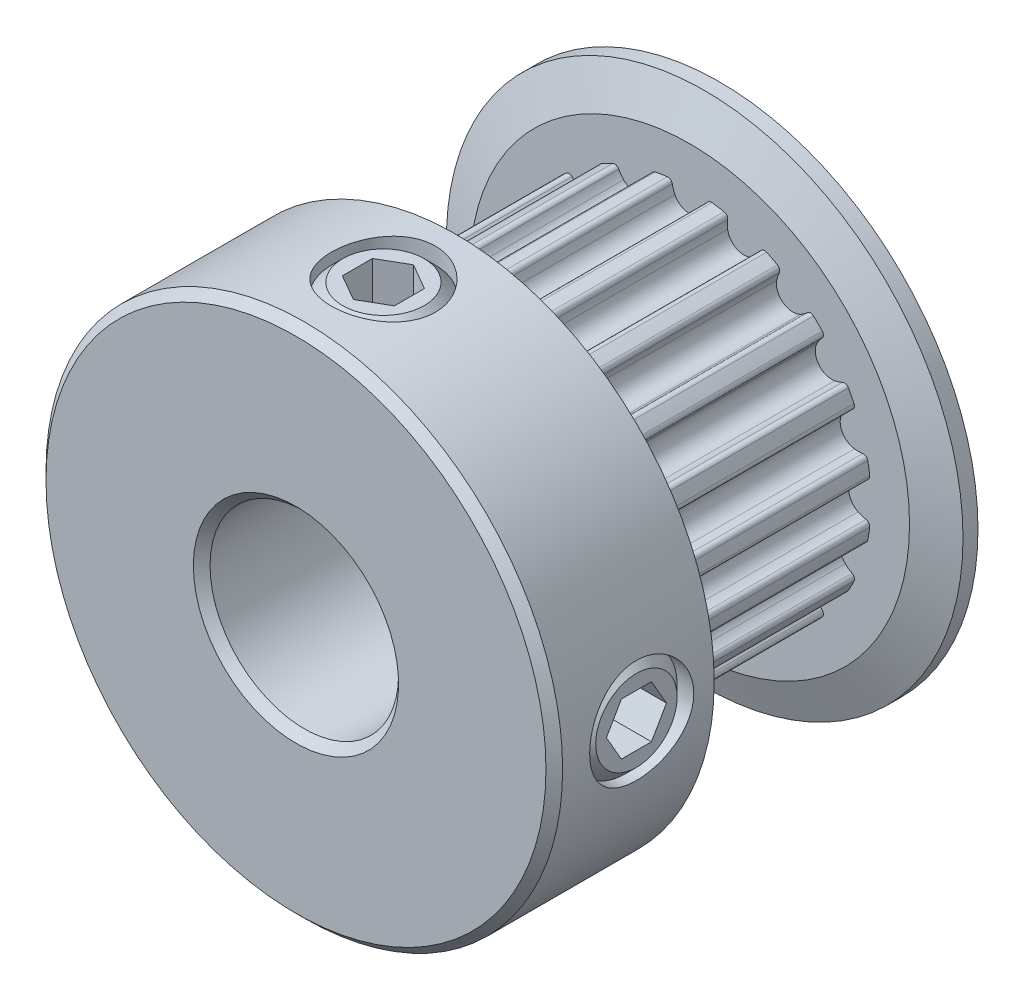
SolidWorks part; units mm, degrees
ref_plane "Front Plane" through (0, 0, 0) normal (0, 0, 1) x (1, 0, 0)
ref_plane "Top Plane" through (0, 0, 0) normal (0, 1, 0) x (1, 0, 0)
ref_plane "Right Plane" through (0, 0, 0) normal (1, 0, 0) x (0, 0, -1)
sketch "Sketch1" plane through (0, 0, 0) normal (0, 0, 1) x (1, 0, 0)
  line L1 (-1.7499, 5.3585) -> (1.7499, 5.3585) construction
  line L4 (0, 0) -> (0, 5.3585) construction
  line L5 (0, 5.3585) -> (0, 11.2113) construction
  line L6 (0, 6.3625) -> (1.9751, 6.0482) construction
  line L7 (1.9751, 6.0482) -> (2.6648, 5.8229) construction
  line L8 (1.9751, 6.0482) -> (1.7499, 5.3585) construction
  line L9 (-1.9751, 6.0482) -> (-1.7499, 5.3585) construction
  line L10 (-1.8963, 5.8067) -> (-2.841, 8.6995)
  line L11 (-2.841, 8.6995) -> (2.841, 8.6995)
  line L12 (2.841, 8.6995) -> (1.8963, 5.8067)
  circle A0 centre (0, 0) radius 6.3625 construction
  circle A1 centre (0, 0) radius 8.6995 construction
  circle A2 centre (0, 0) radius 6.1085 construction
  arc A3 (-0.4989, 5.6703) -> (0.4989, 5.6703) centre (0, 5.9135) ccw
  arc A4 (-0.4989, 5.6703) -> (-0.5855, 5.9387) centre (0.4, 6.1085) cw
  arc A5 (-1.8963, 5.8067) -> (-0.7518, 6.0621) centre (0, 0) cw
  arc A6 (-0.5855, 5.9387) -> (-0.7518, 6.0621) centre (-0.7333, 5.9132) ccw
  arc A7 (1.8963, 5.8067) -> (0.7518, 6.0621) centre (0, 0) ccw
  arc A8 (0.5855, 5.9387) -> (0.7518, 6.0621) centre (0.7333, 5.9132) cw
  arc A9 (0.4989, 5.6703) -> (0.5855, 5.9387) centre (-0.4, 6.1085) ccw
  point P6 (0, 20.9083)
  point P11 (0, 6.3625)
  point P13 (0, 8.6995)
  point P14 (0, 6.1085)
  dimension "D1" = 9.697
  dimension "D2" = 4.8488
sketch "Sketch2" plane through (0, 0, 0) normal (1, 0, 0) x (0, 0, -1)
  line L0 (-7.135, 3.175) -> (7.135, 3.175)
  line L1 (-7.135, 3.175) -> (-7.135, 8.6995)
  line L2 (-1.75, 8.6995) -> (-7.135, 8.6995)
  line L3 (-2.255, 3.175) -> (-2.255, 8.6995) construction
  line L4 (-2.255, 8.6995) -> (-1.245, 8.6995) construction
  line L5 (-1.245, 8.6995) -> (-1.245, 6.1085) construction
  line L6 (-1.245, 6.1085) -> (6.125, 6.1085)
  line L7 (6.125, 6.1085) -> (6.125, 8.6995) construction
  line L8 (6.125, 8.6995) -> (7.135, 8.6995) construction
  line L9 (7.135, 8.6995) -> (7.135, 3.175)
  line L10 (-7.135, 0) -> (7.135, 0) construction
  line L11 (6.63, 8.6995) -> (6.125, 7.404)
  line L12 (-1.245, 7.404) -> (-1.75, 8.6995)
  line L14 (-1.245, 7.404) -> (-1.245, 6.1085)
  line L15 (6.125, 6.1085) -> (6.125, 7.404)
  line L16 (6.63, 8.6995) -> (7.135, 8.6995)
  arc A0 (-1.245, 7.404) -> (-1.75, 8.6995) centre (-3.1592, 7.404) ccw construction
  arc A1 (6.125, 7.404) -> (6.63, 8.6995) centre (8.0392, 7.404) cw construction
  point P12 (-1.245, 7.404)
  point P14 (-1.75, 8.6995)
  point P20 (6.125, 7.404)
  point P21 (6.63, 8.6995)
  point P25 (6.125, 0)
  point P26 (-1.245, 0)
  dimension "OA" = 14.27
  dimension "Bore" = 6.35
  dimension "Outside Width" = 8.38
  dimension "Inside Width" = 7.37
revolve "Revolve1" add sketch "Sketch2" angle 360 mid plane about L10
sketch "Sketch3" plane through (0, 0, 0) normal (0, 0, 1) x (1, 0, 0)
  line L6 (2.841, 8.6995) -> (-2.841, 8.6995)
  line L7 (1.8963, 5.8067) -> (2.841, 8.6995)
  line L8 (-2.841, 8.6995) -> (-1.8963, 5.8067)
  line L9 (2.841, 8.6995) -> (-2.841, 8.6995)
  line L10 (1.8963, 5.8067) -> (2.841, 8.6995)
  line L11 (-2.841, 8.6995) -> (-1.8963, 5.8067)
  arc A8 (1.8963, 5.8067) -> (0.7518, 6.0621) centre (0, 0) ccw
  arc A9 (0.7518, 6.0621) -> (0.5855, 5.9387) centre (0.7333, 5.9132) ccw
  arc A10 (0.4989, 5.6703) -> (0.5855, 5.9387) centre (-0.4, 6.1085) ccw
  arc A11 (-0.4989, 5.6703) -> (0.4989, 5.6703) centre (0, 5.9135) ccw
  arc A12 (-0.5855, 5.9387) -> (-0.4989, 5.6703) centre (0.4, 6.1085) ccw
  arc A13 (-0.5855, 5.9387) -> (-0.7518, 6.0621) centre (-0.7333, 5.9132) ccw
  arc A14 (-0.7518, 6.0621) -> (-1.8963, 5.8067) centre (0, 0) ccw
  arc A15 (1.8963, 5.8067) -> (0.7518, 6.0621) centre (0, 0) ccw
  arc A16 (0.7518, 6.0621) -> (0.5855, 5.9387) centre (0.7333, 5.9132) ccw
  arc A17 (0.4989, 5.6703) -> (0.5855, 5.9387) centre (-0.4, 6.1085) ccw
  arc A18 (-0.4989, 5.6703) -> (0.4989, 5.6703) centre (0, 5.9135) ccw
  arc A19 (-0.5855, 5.9387) -> (-0.4989, 5.6703) centre (0.4, 6.1085) ccw
  arc A20 (-0.5855, 5.9387) -> (-0.7518, 6.0621) centre (-0.7333, 5.9132) ccw
  arc A21 (-0.7518, 6.0621) -> (-1.8963, 5.8067) centre (0, 0) ccw
  dimension "D1" = 0
extrude "Cut-Extrude1" cut sketch "Sketch3" against normal up to vertex (6.125 mm away) from vertex up to point (0, 6.1085, -6.125) starting at point (0, 6.1085, 1.245)
pattern_circular "CirPattern1" count 20 over 360 about axis through (0, 0, 7.135) along (0, 0, 1) of "Cut-Extrude1"
sketch "Sketch4" plane through (0, 0, 0) normal (1, 0, 0) x (0, -1, 0)
  line L0 (0, -1.245) -> (0, -7.135) construction
  line L1 (-3.175, -7.135) -> (3.175, -7.135) construction
  line L2 (7.404, -1.245) -> (-7.404, -1.245) construction
  circle A0 centre (0, -4.19) radius 1.7526
extrude "Cut-Extrude2" cut sketch "Sketch4" along normal through all
ref_plane "Plane1" through (0, 0, 4.19) normal (0, 0, 1) x (1, 0, 0)
sketch "Sketch5" plane through (0, 0, 4.19) normal (0, 0, 1) x (1, 0, 0)
  line L0 (0, 0) -> (0, 8.6995) construction
  line L1 (3.175, -1.3716) -> (3.175, 0)
  line L2 (3.556, -1.7526) -> (8.1401, -1.7526)
  line L3 (3.175, 0) -> (8.6995, 0) construction
  line L4 (3.175, 0) -> (8.5211, 0)
  line L5 (8.5211, 0) -> (8.5211, -1.3716)
  line L6 (3.556, -1.7526) -> (3.175, -1.3716)
  line L7 (8.5211, -1.3716) -> (8.1401, -1.7526)
  circle A0 centre (0, 0) radius 8.6995 construction
  circle A1 centre (0, 0) radius 3.175 construction
  point P2 (3.175, -1.7526)
  point P11 (8.5211, -1.7526)
revolve "Revolve2" add sketch "Sketch5" angle 360 mid plane about L4
sketch "Sketch6" plane through (8.5211, 5.3841, 0) normal (-1, 0, 0) x (0, -1, 0)
  line L1 (5.3841, 5.2019) -> (4.5078, 4.6959)
  line L2 (4.5078, 4.6959) -> (4.5078, 3.6841)
  line L3 (4.5078, 3.6841) -> (5.3841, 3.1781)
  line L4 (5.3841, 3.1781) -> (6.2604, 3.6841)
  line L5 (6.2604, 3.6841) -> (6.2604, 4.6959)
  line L6 (6.2604, 4.6959) -> (5.3841, 5.2019)
  circle A0 centre (5.3841, 4.19) radius 0.8763 construction
  dimension "D1" = 1.7526
extrude "Cut-Extrude3" cut sketch "Sketch6" along normal blind 1.3144
pattern_circular "CirPattern3" count 2 over 90 about axis through (0, 0, 7.135) along (0, 0, 1) of "Cut-Extrude2", "Revolve2", "Cut-Extrude3"
chamfer "Chamfer1" distance 0.2807 angle 45 2 edges at (3.175, 0, 7.135) (8.6995, 0, 7.135)
ref_axis "Center Axis 1" through (0, 0, -7.135) along (0, 0, 1)
ref_plane "Contact Plane 1" through (0, 0, 7.135) normal (0, 0, 1) x (1, 0, 0)
ref_plane "Contact Plane 2" through (0, 0, -7.135) normal (0, 0, -1) x (-1, 0, 0)
equation "\"D2@Sketch1\"= \"D1@Sketch1\" / 2"
equation "\"D1@Sketch6\" = \"Set Screw@Sketch4\" / 2"
equation "\"D1@Cut-Extrude3\" = \"D1@Sketch6\"*.75"
